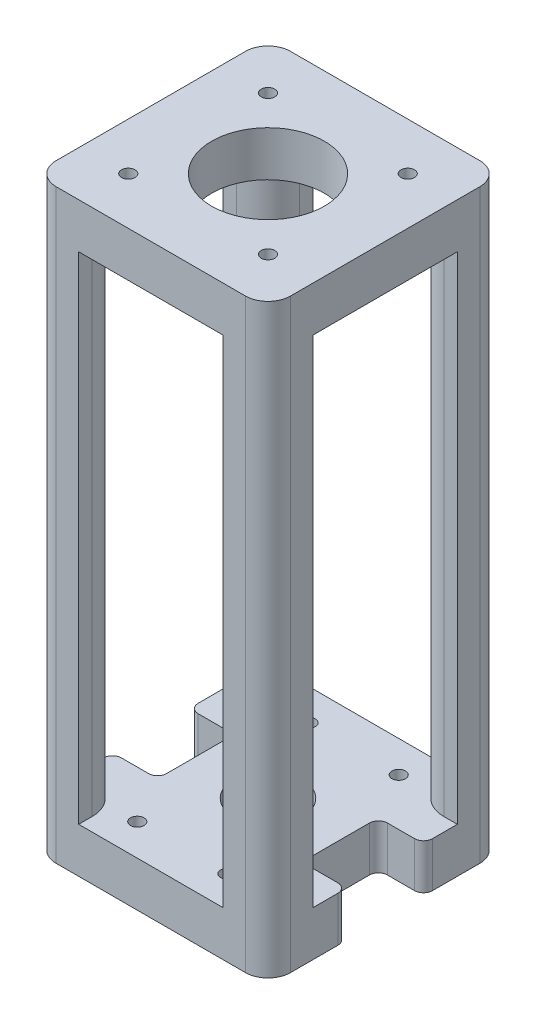
SolidWorks part; units mm, degrees
ref_plane "Front Plane" through (0, 0, 0) normal (0, 0, 1) x (1, 0, 0)
ref_plane "Top Plane" through (0, 0, 0) normal (0, 1, 0) x (1, 0, 0)
ref_plane "Right Plane" through (0, 0, 0) normal (1, 0, 0) x (0, 0, -1)
sketch "Sketch1" plane through (0, 0, 0) normal (0, 1, 0) x (1, 0, 0)
  line L1 (-26, 26) -> (26, 26)
  line L2 (-26, 26) -> (-26, -26)
  line L3 (-26, -26) -> (26, -26)
  line L4 (26, 26) -> (26, -26)
  line L5 (-26, 26) -> (26, -26) construction
  line L6 (-26, -26) -> (26, 26) construction
  point P0 (0, 0)
  dimension "D1" = 52
  dimension "D2" = 52
extrude "Boss-Extrude1" add sketch "Sketch1" along normal blind 10
sketch "Sketch2" plane through (0, 10, 0) normal (0, 1, 0) x (1, 0, 0)
  line L0 (0, 26) -> (0, -26) construction
  line L1 (-26, 26) -> (-16, 26)
  line L2 (-26, 26) -> (-26, 16)
  line L3 (-26, 16) -> (-16, 16)
  line L4 (-16, 26) -> (-16, 16)
  line L6 (26, 26) -> (-26, 26) construction
  line L7 (-26, -26) -> (26, -26) construction
  line L8 (-26, 0) -> (26, 0) construction
  line L9 (-26, 26) -> (-26, -26) construction
  line L10 (26, -26) -> (26, 26) construction
  line L11 (16, 26) -> (16, 16)
  line L12 (26, 16) -> (16, 16)
  line L13 (26, 26) -> (26, 16)
  line L14 (26, 26) -> (16, 26)
  line L15 (-26, -26) -> (-16, -26)
  line L16 (-26, -26) -> (-26, -16)
  line L17 (-16, -26) -> (-16, -16)
  line L18 (-26, -16) -> (-16, -16)
  line L19 (26, -16) -> (16, -16)
  line L20 (26, -26) -> (26, -16)
  line L21 (26, -26) -> (16, -26)
  line L22 (16, -26) -> (16, -16)
  dimension "D1" = 10
  dimension "D2" = 10
extrude "Boss-Extrude2" add sketch "Sketch2" along normal blind 110
sketch "Sketch3" plane through (0, 120, 0) normal (0, 1, 0) x (1, 0, 0)
  line L4 (26, -26) -> (26, 26)
  line L5 (-26, -26) -> (26, -26)
  line L6 (-26, 26) -> (-26, -26)
  line L7 (26, 26) -> (-26, 26)
  line L8 (26, -26) -> (26, 26)
  line L9 (-26, -26) -> (26, -26)
  line L10 (-26, 26) -> (-26, -26)
  line L11 (26, 26) -> (-26, 26)
  dimension "D1" = 0
extrude "Boss-Extrude3" add sketch "Sketch3" along normal blind 10
sketch "Sketch4" plane through (0, 130, 0) normal (0, 1, 0) x (1, 0, 0)
  circle A0 centre (0, 0) radius 12.5
  dimension "D1" = 25
extrude "Cut-Extrude1" cut sketch "Sketch4" against normal up to surface (10 mm away) up to face at (0, 120, 0)
sketch "Sketch5" plane through (0, 0, 0) normal (0, -1, 0) x (1, 0, 0)
  circle A0 centre (0, 0) radius 7.5
  dimension "D1" = 15
extrude "Cut-Extrude2" cut sketch "Sketch5" against normal up to surface (10 mm away) up to face at (0, 10, 0)
sketch "Sketch6" plane through (0, 0, 0) normal (0, -1, 0) x (1, 0, 0)
  line L0 (-26, -26) -> (-26, 26) construction
  line L1 (-26, -8.5) -> (-16, -8.5)
  line L2 (-26, -8.5) -> (-26, 8.5)
  line L3 (-26, 8.5) -> (-16, 8.5)
  line L4 (-16, -8.5) -> (-16, 8.5)
  line L5 (0, 26) -> (0, -26) construction
  line L6 (-26, 26) -> (26, 26) construction
  line L7 (26, -26) -> (-26, -26) construction
  line L8 (26, 8.5) -> (16, 8.5)
  line L9 (16, -8.5) -> (16, 8.5)
  line L10 (26, -8.5) -> (16, -8.5)
  line L11 (26, -8.5) -> (26, 8.5)
  point P6 (-26, 0)
  dimension "D1" = 17
  dimension "D2" = 10
extrude "Cut-Extrude3" cut sketch "Sketch6" against normal up to surface (10 mm away) up to face at (0, 10, 7.5)
sketch "Sketch7" plane through (0, 0, 0) normal (0, -1, 0) x (1, 0, 0)
  line L0 (0, 26) -> (0, -26) construction
  line L1 (-26, 26) -> (26, 26) construction
  line L2 (26, -26) -> (-26, -26) construction
  line L3 (-26, 0) -> (26, 0) construction
  line L4 (-26, -16) -> (-26, 16) construction
  line L5 (26, 16) -> (26, -16) construction
  circle A0 centre (10, 19) radius 1.5
  circle A1 centre (-10, 19) radius 1.5
  circle A2 centre (10, -19) radius 1.5
  circle A3 centre (-10, -19) radius 1.5
  dimension "D1" = 3
  dimension "D2" = 10
  dimension "D3" = 19
extrude "Cut-Extrude4" cut sketch "Sketch7" against normal up to surface (10 mm away) up to face at (0, 10, 0)
fillet "Fillet1" radius 5 4 edges at (26, 65, 26) (26, 65, -26) (-26, 65, -26) (-26, 65, 26)
fillet "Fillet2" radius 2 8 edges at (26, 5, -8.5) (26, 5, 8.5) (-26, 5, -8.5) (-26, 5, 8.5) (-16, 5, -8.5) (-16, 5, 8.5) (16, 5, -8.5) (16, 5, 8.5)
sketch "Sketch8" plane through (0, 130, 0) normal (0, 1, 0) x (1, 0, 0)
  line L0 (0, 26) -> (0, -26)
  line L1 (21, 26) -> (-21, 26) construction
  line L2 (-21, -26) -> (21, -26) construction
  line L3 (-26, 0) -> (26, 0)
  line L4 (-26, 21) -> (-26, -21) construction
  line L5 (26, -21) -> (26, 21) construction
  circle A0 centre (15.5, 15.5) radius 1.5
  circle A1 centre (-15.5, 15.5) radius 1.5
  circle A2 centre (15.5, -15.5) radius 1.5
  circle A3 centre (-15.5, -15.5) radius 1.5
  point P14 (0, 0)
  dimension "D1" = 3
  dimension "D2" = 15.5
  dimension "D3" = 15.5
extrude "Cut-Extrude6" cut sketch "Sketch8" against normal up to surface (10 mm away) contours A3 | A1 | A0 | A2 region at (15.5, 130, -15.5) region at (-15.5, 130, -15.5) region at (15.5, 130, 15.5) region at (-15.5, 130, 15.5) up to face at (0, 120, 12.5)
fillet "Fillet4" radius 7 4 edges at (16, 65, -16) (16, 65, 16) (-16, 65, 16) (-16, 65, -16)
